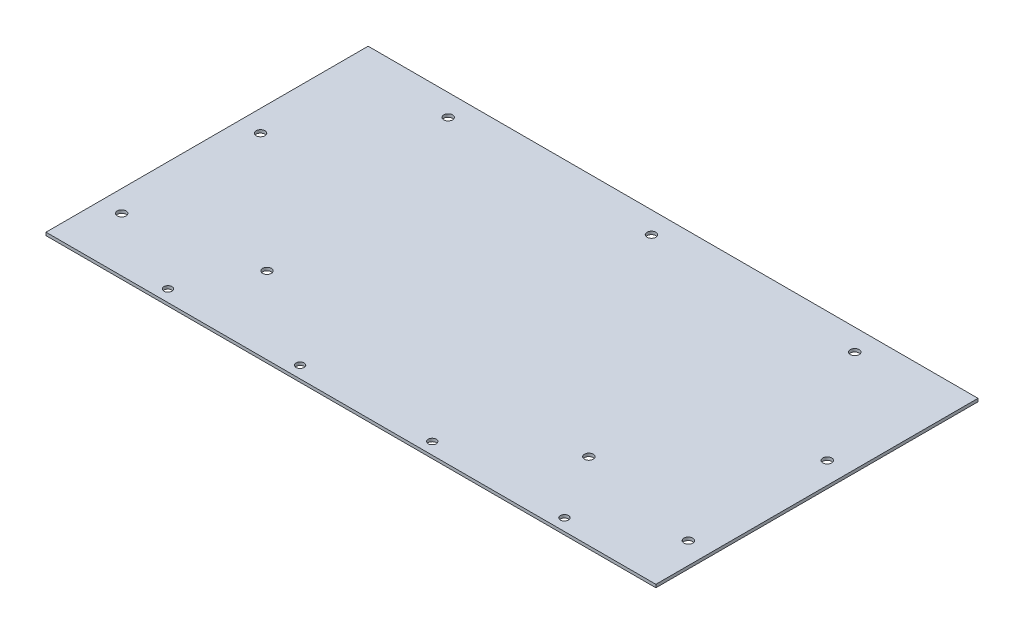
SolidWorks part; units mm, degrees
material "6061-T6 (SS)"
ref_plane "X-Y Datum" through (0, 0, 0) normal (0, 0, 1) x (1, 0, 0)
ref_plane "X-Z Datum" through (0, 0, 0) normal (0, 1, 0) x (1, 0, 0)
ref_plane "Y-Z Datum" through (0, 0, 0) normal (1, 0, 0) x (0, 0, -1)
sketch "Sketch1" plane through (0, 0, 0) normal (0, 0, 1) x (1, 0, 0)
  line L1 (-228.6, -1.143) -> (228.6, -1.143)
  line L2 (-228.6, -1.143) -> (-228.6, 1.143)
  line L3 (-228.6, 1.143) -> (228.6, 1.143)
  line L4 (228.6, -1.143) -> (228.6, 1.143)
  line L5 (-228.6, -1.143) -> (228.6, 1.143) construction
  line L6 (-228.6, 1.143) -> (228.6, -1.143) construction
  point P0 (0, 0)
  dimension "D1" = 2.286
  dimension "D2" = 457.2
extrude "Boss-Extrude1" add sketch "Sketch1" along normal blind 238.3152
sketch "Sketch2" plane through (0, 0, 0) normal (0, 0, -1) x (-1, 0, 0)
  line L22 (-228.6, 1.143) -> (-228.6, -1.143)
  line L23 (-228.6, -1.143) -> (228.6, -1.143)
  line L24 (228.6, -1.143) -> (228.6, 1.143)
  line L25 (228.6, 1.143) -> (-228.6, 1.143)
  line L26 (-228.6, 1.143) -> (-228.6, -1.143)
  line L27 (-228.6, -1.143) -> (228.6, -1.143)
  line L28 (228.6, -1.143) -> (228.6, 1.143)
  line L29 (228.6, 1.143) -> (-228.6, 1.143)
  line M6 (-228.6, -1.143) -> (228.6, -1.143)
  line M8 (228.6, 1.143) -> (-228.6, 1.143)
  dimension "D1" = 0
extrude "Boss-Extrude2" add sketch "Sketch2" along normal blind 3.175 contours M8 M6 | M8 M6 region at (0, 0, 0)
sketch "Sketch9" plane through (0, 1.143, 0) normal (0, 1, 0) x (1, 0, 0)
  line L0 (-146.05, -238.3152) -> (-146.05, -229.4252) construction
  line L1 (228.6, -238.3152) -> (-228.6, -238.3152) construction
  line L2 (-228.6, -238.3152) -> (-228.6, 3.175) construction
  circle A0 centre (-146.05, -229.4252) radius 3
  dimension "D2" = 82.55
  dimension "D3" = 6
  dimension "D1" = 8.89
extrude "Cut-Extrude10" cut sketch "Sketch9" against normal blind 2.54
pattern_linear "LPattern1" count 4 spacing 99.06 along (1, 0, 0) of "Cut-Extrude10"
sketch "Sketch10" plane through (0, -1.143, 0) normal (0, -1, 0) x (1, 0, 0)
  circle A0 centre (151.13, 229.4252) radius 3 construction
  circle A1 centre (52.07, 229.4252) radius 3 construction
  circle A2 centre (-46.99, 229.4252) radius 3 construction
  circle A3 centre (-146.05, 229.4252) radius 3 construction
  circle A4 centre (151.13, 229.4252) radius 3
  circle A5 centre (52.07, 229.4252) radius 3
  circle A6 centre (-46.99, 229.4252) radius 3
  circle A7 centre (-146.05, 229.4252) radius 3
sketch "Sketch12" plane through (0, -1.143, 0) normal (0, -1, 0) x (1, 0, 0)
  point P0 (-212.419, 93.6448)
  point P1 (-152.4, 13.0175)
  point P3 (0, 13.0175)
  point P5 (152.4, 13.0175)
  point P7 (212.419, 93.6448)
  point P9 (212.419, 197.7848)
  point P11 (120.65, 180.586)
  point P15 (-120.65, 180.586)
  point P17 (-212.419, 197.7848)
hole_wizard "M6 Clearance Hole1" positions "Sketch12" profile "Sketch13" hole size "M6" standard "ANSI Metric" end condition through all
sketch "Sketch13" plane through (-212.419, -1.143, 93.6448) normal (1, 0, 0) x (0, 0, -1)
  line L0 (0, 0) -> (0, 2.286)
  line L1 (0, 2.286) -> (3.3, 2.286)
  line L2 (3.3, 2.286) -> (3.3, 0)
  line L5 (3.3, 0) -> (0, 0)
  line L11 (0, -6.35) -> (0, 107.95) construction
  dimension "Thru Hole Dia." = 6.6
  dimension "Thru Hole Depth" = 2.286
